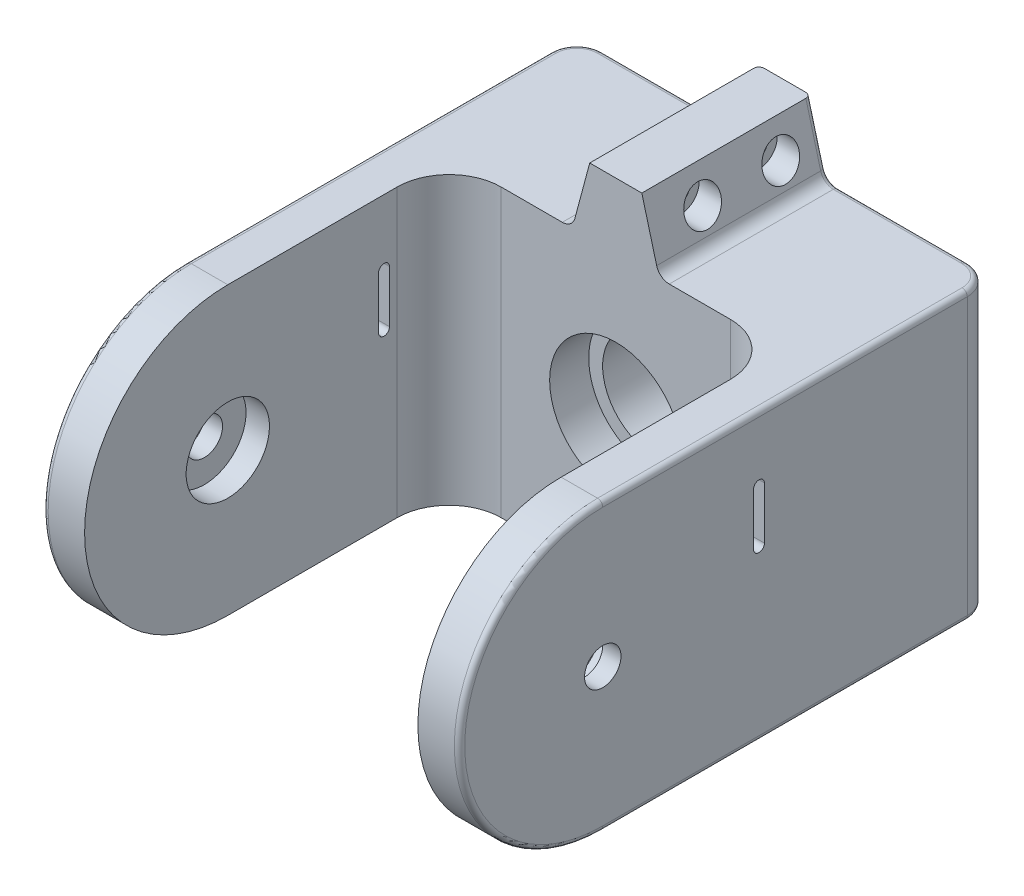
SolidWorks part; units mm, degrees
ref_plane "Front Plane" through (0, 0, 0) normal (0, 0, 1) x (1, 0, 0)
ref_plane "Top Plane" through (0, 0, 0) normal (0, 1, 0) x (1, 0, 0)
ref_plane "Right Plane" through (0, 0, 0) normal (1, 0, 0) x (0, 0, -1)
sketch "Sketch1" plane through (0, 0, 0) normal (0, 0, 1) x (1, 0, 0)
  circle A2 centre (0, 0) radius 25.4
  circle A3 centre (0, 0) radius 25.4 construction
  circle A4 centre (0, 0) radius 20.05
  circle A5 centre (0, 0) radius 19.05 construction
  dimension "D1" = 1
extrude "Centre Hole for L2" add sketch "Sketch1" along normal blind 30 contours A4 | A2
sketch "Sketch2" plane through (0, 0, 30) normal (0, 0, 1) x (1, 0, 0)
  line L0 (0, 48.4974) -> (0, 0) construction
  line L5 (-80, 55) -> (-80, -55)
  line L12 (0, 0) -> (72.986, 0) construction
  line L16 (-80, 55) -> (80, 55)
  line L17 (80, 55) -> (80, -55)
  line L18 (-80, -55) -> (80, -55)
  circle A0 centre (0, 0) radius 25.4
  circle A1 centre (0, 0) radius 25.4 construction
  circle A5 centre (0, 0) radius 25.4
  point P13 (0, 55)
  dimension "D1" = 80
  dimension "D2" = 110
extrude "Main Structure" add sketch "Sketch2" along normal blind 100 and the other way blind 50 separate body contours L5 L18 L17 L16 | A5
sketch "Sketch3" plane through (-80, 0, 0) normal (-1, 0, 0) x (0, 0, 1)
  line L0 (130, 55) -> (130, -55) construction
  line L1 (130, 55) -> (130, -55)
  line L2 (-20, 55) -> (130, 55) construction
  arc A0 (130, 55) -> (130, -55) centre (130, 0) cw
extrude "Bearing Curve" add sketch "Sketch3" against normal blind 16 contours A0 L1
mirror "Upright Mirror" about plane through (0, 0, 0) normal (1, 0, 0) of "Bearing Curve"
sketch "Sketch6" plane through (-80, 0, 0) normal (-1, 0, 0) x (0, 0, 1)
  circle A0 centre (130, 0) radius 7
  dimension "D1" = 14
extrude "Shaft Hole" cut sketch "Sketch6" against normal up to surface (16 mm away) up to face at (-64, 0, 157.5)
sketch "Sketch4" plane through (0, 55, 0) normal (0, 1, 0) x (1, 0, 0)
  line L0 (0, -110) -> (0, 20) construction
  line L1 (-64, -130) -> (64, -130) construction
  line L2 (-80, 20) -> (80, 20) construction
  line L3 (-64, -130) -> (-64, -65)
  line L4 (-44, -45) -> (44, -45)
  line L5 (-64, -130) -> (64, -130)
  line L6 (64, -130) -> (64, -65)
  arc A0 (-64, -65) -> (-44, -45) centre (-44, -65) cw
  arc A1 (64, -65) -> (44, -45) centre (44, -65) ccw
  point P17 (0, -130)
  point P20 (0, -45)
  dimension "D2" = 20
  dimension "D1" = 65
extrude "Wrist Cutout" cut sketch "Sketch4" against normal through all
sketch "Sketch9" plane through (-64, 0, 0) normal (1, 0, 0) x (0, 0, -1)
  circle A0 centre (-130, 0) radius 16
  dimension "D1" = 32
extrude "Bearing" cut sketch "Sketch9" against normal blind 9
mirror "Bearing Mirror" about plane through (0, 0, 0) normal (1, 0, 0) of "Shaft Hole", "Bearing"
fillet "Fillet2" radius 10 2 edges at (-80, 0, -20) (80, 0, -20)
sketch "Sketch10" plane through (0, 0, -20) normal (0, 0, -1) x (-1, 0, 0)
  line L0 (0, 55) -> (0, 80) construction
  line L1 (70, 55) -> (-70, 55) construction
  line L2 (10, 80) -> (-10, 80)
  line L3 (-10, 80) -> (-16.6987, 55)
  line L4 (-16.6987, 55) -> (16.6987, 55)
  line L5 (10, 80) -> (16.6987, 55)
  dimension "D1" = 25
  dimension "D2" = 10
  dimension "D3" = 75
extrude "Bolt Structure" add sketch "Sketch10" against normal up to surface (65 mm away) up to face at (0, 0, 45)
sketch "Sketch11" plane through (0, 0, 0) normal (1, 0, 0) x (0, 0, -1)
  line L1 (-45, 67.5) -> (20, 67.5) construction
  line L2 (-45, 55) -> (-45, 80) construction
  line L3 (20, 80) -> (20, 55) construction
  circle A1 centre (5, 67.5) radius 3.1
  circle A2 centre (-25, 67.5) radius 3.1
  dimension "D1" = 6.2
  dimension "D2" = 15
  dimension "D3" = 30
extrude "Cut-Extrude6" cut sketch "Sketch11" against normal through all both and the other way through all
sketch "Sketch13" plane through (0, 0, 0) normal (1, 0, 0) x (0, 0, -1)
  circle A0 centre (5, 67.5) radius 7
  circle A1 centre (-25, 67.5) radius 7
  dimension "D1" = 14
extrude "Cut-Extrude8" cut sketch "Sketch13" along normal up to surface (8.3494 mm away) from offset 5 up to face at (14.18, 64.4, -5)
mirror "Mirror8" about plane through (0, 0, 0) normal (0, 1, 0) of "Cut-Extrude6", "Cut-Extrude8", "Bolt Structure"
fillet "Fillet3" radius 5 4 edges at (-16.6987, -55, 12.5) (16.6987, -55, 12.5) (-16.6987, 55, 12.5) (16.6987, 55, 12.5)
fillet "Fillet1" radius 2 22 edges at (-80, 55, 60) (-80, -55, 60) (80, -55, 60) (80, 55, 60) (-80, 0, 185) (-12.8529, -69.353, -20) (-17.4916, -56.0332, -20) (-45.2677, -55, -20) (-77.0711, -55, -17.0711) (-12.8529, 69.353, -20) (-17.4916, 56.0332, -20) (-45.2677, 55, -20) (-77.0711, 55, -17.0711) (12.8529, 69.353, -20) (17.4916, 56.0332, -20) (45.2677, 55, -20) (77.0711, 55, -17.0711) (12.8529, -69.353, -20) (17.4916, -56.0332, -20) (45.2677, -55, -20) (77.0711, -55, -17.0711) (80, 0, 185)
sketch "Sketch14" plane through (-80, 0, 0) normal (-1, 0, 0) x (0, 0, 1)
  line L0 (70, 30) -> (70, 10) construction
  line L1 (72.1, 30) -> (72.1, 10)
  line L2 (67.9, 30) -> (67.9, 10)
  arc A0 (72.1, 30) -> (67.9, 30) centre (70, 30) ccw
  arc A1 (67.9, 10) -> (72.1, 10) centre (70, 10) ccw
  point P2 (70, 20)
  point P7 (0, 0)
  point P8 (0, 0)
  point P9 (0, 0)
  point P11 (0, 0)
  dimension "D1" = 4.2
  dimension "D2" = 20
  dimension "D3" = 10
  dimension "D4" = 70
extrude "Tensioner Slot" cut sketch "Sketch14" against normal up to surface (16 mm away) up to face at (-64, 0, 114)
mirror "Mirror9" about plane through (0, 0, 0) normal (1, 0, 0) of "Tensioner Slot"
